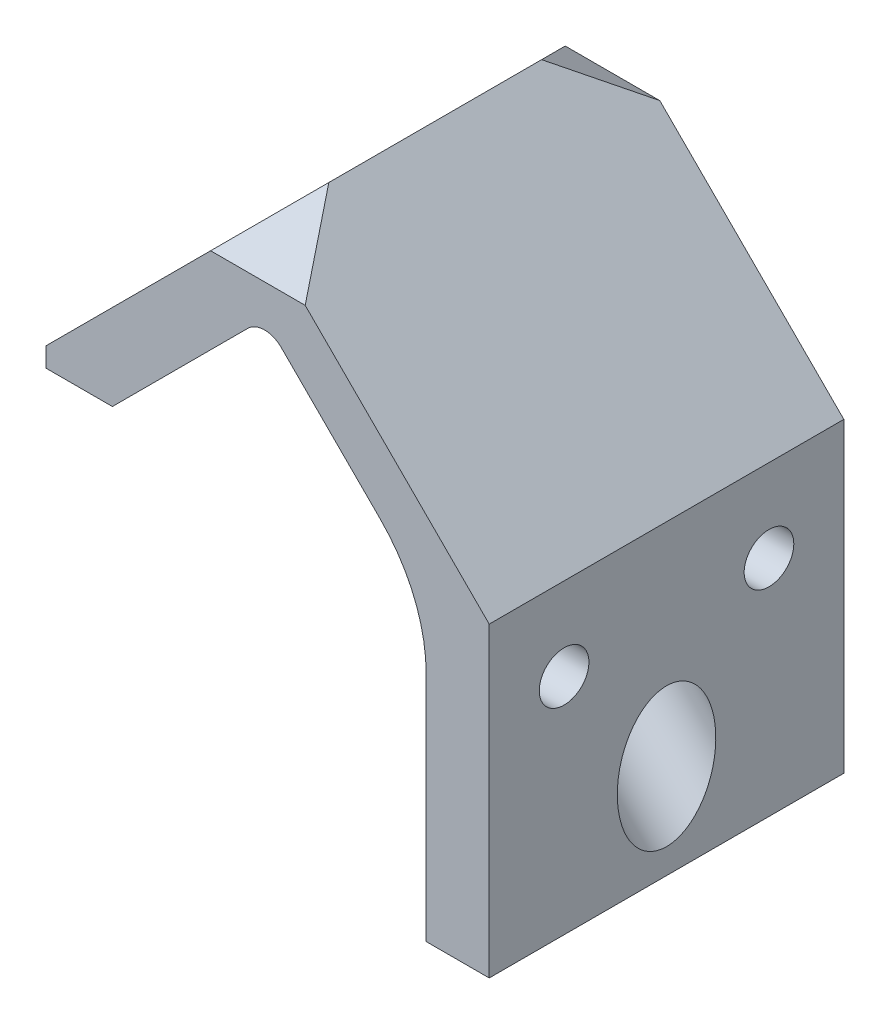
SolidWorks part; units mm, degrees
material "PA 类型 6"
ref_plane "前视基准面" through (0, 0, 0) normal (0, 0, 1) x (1, 0, 0)
ref_plane "上视基准面" through (0, 0, 0) normal (0, 1, 0) x (1, 0, 0)
ref_plane "右视基准面" through (0, 0, 0) normal (1, 0, 0) x (0, 0, -1)
sketch "草图1" plane through (0, 0, 0) normal (0, 0, 1) x (1, 0, 0)
  line L0 (0, 0) -> (144.3086, 0) construction
  line L1 (0, 0) -> (0, 98.9497) construction
  line L4 (14.253, 0) -> (14.253, -19.4462)
  line L5 (14.253, -19.4462) -> (10.253, -19.4462)
  line L6 (10.253, -19.4462) -> (10.253, -0.5962)
  line L7 (10.253, -0.5962) -> (0, 9.6569)
  line L8 (0, 9.6569) -> (-9.6569, 0)
  line L9 (-9.6569, 0) -> (-13.8593, 0)
  line L10 (-13.8593, 0) -> (-13.8593, 1.2423)
  line L11 (-13.8593, 1.2423) -> (-0.4243, 14.6773)
  line L12 (-0.4243, 14.6773) -> (14.253, 0)
  line L13 (-7.1418, 7.9598) -> (-5.4831, 6.3011) construction
  dimension "D1" = 3.85
  dimension "D2" = 3.25
  dimension "D3" = 45
  dimension "D4" = 6.25
  dimension "D5" = 4
  dimension "D6" = 18.85
  dimension "D7" = 14.5
extrude "主结构" add sketch "草图1" along normal blind 22.5
sketch "草图2" plane through (-7.5508, 7.5508, 0) normal (-0.7071, 0.7071, 0) x (0, 0, 1)
  line L0 (22.5, 10.0784) -> (22.5, -8.9216) construction
  line L1 (22.5, 0.5784) -> (0, 0.5784) construction
  line L2 (0, 10.0784) -> (0, -8.9216) construction
  circle A0 centre (11.25, 0.5784) radius 3.125
  dimension "D1" = 6.25
extrude "SMA接口" cut sketch "草图2" against normal through all
sketch "草图3" plane through (14.253, 0, 0) normal (1, 0, 0) x (0, 0, -1)
  line L0 (-22.5, -5.25) -> (0, -5.25) construction
  line L1 (-22.5, -19.4462) -> (-22.5, 0) construction
  line L2 (0, -19.4462) -> (0, 0) construction
  line L3 (-11.25, -5.25) -> (-11.25, -23.4325) construction
  line L4 (-22.5, 0) -> (0, 0) construction
  circle A0 centre (-17.75, -5.25) radius 1.575
  circle A1 centre (-4.75, -5.25) radius 1.575
  dimension "D2" = 3.15
  dimension "D1" = 6.5
  dimension "D3" = 5.25
extrude "侧板接口" cut sketch "草图3" against normal through all
sketch "草图4" plane through (10.253, 0, 0) normal (-1, 0, 0) x (0, 0, 1)
  line L1 (6.3377, -8) -> (7.9254, -5.25)
  line L2 (7.9254, -5.25) -> (6.3377, -2.5)
  line L3 (6.3377, -2.5) -> (3.1623, -2.5)
  line L4 (3.1623, -2.5) -> (1.5746, -5.25)
  line L5 (1.5746, -5.25) -> (3.1623, -8)
  line L6 (3.1623, -8) -> (6.3377, -8)
  line L7 (19.3377, -8) -> (20.9254, -5.25)
  line L8 (20.9254, -5.25) -> (19.3377, -2.5)
  line L9 (19.3377, -2.5) -> (16.1623, -2.5)
  line L10 (16.1623, -2.5) -> (14.5746, -5.25)
  line L11 (14.5746, -5.25) -> (16.1623, -8)
  line L12 (16.1623, -8) -> (19.3377, -8)
  circle A0 centre (4.75, -5.25) radius 2.75 construction
  circle A1 centre (17.75, -5.25) radius 2.75 construction
  circle A2 centre (4.75, -5.25) radius 1.575 construction
  circle A3 centre (17.75, -5.25) radius 1.575 construction
  dimension "D1" = 5.5
extrude "侧板接口-2" cut sketch "草图4" against normal blind 1.25
sketch "造型切除定位-1" plane through (0, 0, 0) normal (0, 0, -1) x (-1, 0, 0)
  line L0 (-2.5757, 11.6773) -> (3.4243, 11.6773)
  line L1 (-14.253, 0) -> (0.4243, 14.6773) construction
  line L2 (0.4243, 14.6773) -> (13.8593, 1.2423) construction
  dimension "D1" = 3
sketch "造型切除定位-2" plane through (-7.5508, 7.5508, 0) normal (-0.7071, 0.7071, 0) x (0, 0, 1)
  line L0 (0, 10.0784) -> (11.25, 10.0784)
  line L1 (22.5, 10.0784) -> (0, 10.0784) construction
  line L2 (0, 10.0784) -> (4.5, 10.0784)
  dimension "D1" = 4.5
ref_plane "中心对称面" through (0, 0, 11.25) normal (0, 0, 1) x (1, 0, 0)
ref_plane "造型切除面定位-1" through (0, 8.0843, -5.3895) normal (0, -0.8321, 0.5547) x (-1, 0, 0)
sketch "草图7" plane through (0, 8.0843, -5.3895) normal (0, -0.8321, 0.5547) x (-1, 0, 0)
  line L0 (0.4243, -11.8857) -> (-2.5757, -6.4774)
  line L1 (-2.5757, -6.4774) -> (3.4243, -6.4774)
  line L2 (3.4243, -6.4774) -> (0.4243, -11.8857)
extrude "造型切除" cut sketch "草图7" against normal through all
mirror "镜向1" about plane through (0, 0, 11.25) normal (0, 0, 1) of "造型切除"
fillet "圆角1" radius 10 1 edges at (10.253, -0.5962, 11.25)
fillet "圆角2" radius 1.5 1 edges at (0, 9.6569, 11.25)
